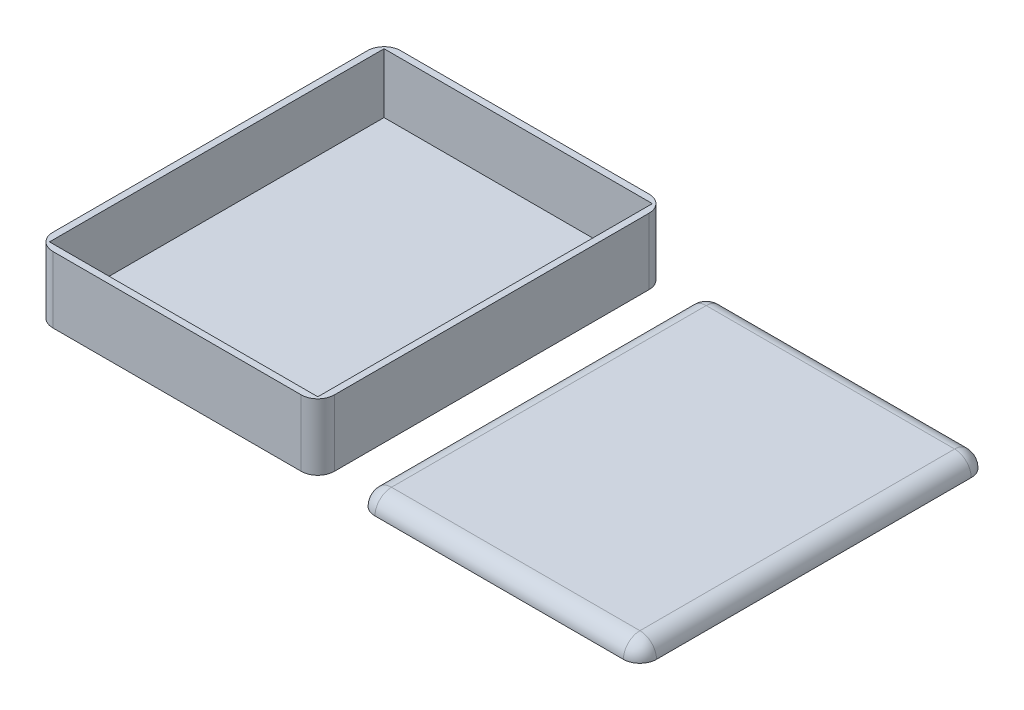
SolidWorks part; units mm, degrees
ref_plane "Front Plane" through (0, 0, 0) normal (0, 0, 1) x (1, 0, 0)
ref_plane "Top Plane" through (0, 0, 0) normal (0, 1, 0) x (1, 0, 0)
ref_plane "Right Plane" through (0, 0, 0) normal (1, 0, 0) x (0, 0, -1)
sketch "Sketch1" plane through (0, 0, 0) normal (0, 1, 0) x (1, 0, 0)
  line L1 (-42.5, -52.5) -> (42.5, -52.5)
  line L2 (-42.5, -52.5) -> (-42.5, 52.5)
  line L3 (-42.5, 52.5) -> (42.5, 52.5)
  line L4 (42.5, -52.5) -> (42.5, 52.5)
  line L5 (-42.5, -52.5) -> (42.5, 52.5) construction
  line L6 (-42.5, 52.5) -> (42.5, -52.5) construction
  point P0 (0, 0)
  dimension "D1" = 85
  dimension "D2" = 105
extrude "Boss-Extrude1" add sketch "Sketch1" along normal blind 20
shell "Shell1" thickness 2 removed face at (0, 20, 0)
sketch "Sketch2" plane through (11.5436, 0, 0) normal (0, 1, 0) x (1, 0, 0)
  line L1 (43.7365, 51.9703) -> (128.7365, 51.9703)
  line L2 (43.7365, 51.9703) -> (43.7365, -53.0297)
  line L3 (43.7365, -53.0297) -> (128.7365, -53.0297)
  line L4 (128.7365, 51.9703) -> (128.7365, -53.0297)
  dimension "D1" = 85
  dimension "D2" = 105
extrude "Boss-Extrude2" add sketch "Sketch2" along normal blind 5 separate body
fillet "Fillet1" radius 5 4 edges at (-42.5, 10, -52.5) (42.5, 10, -52.5) (42.5, 10, 52.5) (-42.5, 10, 52.5)
fillet "Fillet2" radius 5 4 edges at (55.2802, 2.5, -51.9703) (140.2802, 2.5, -51.9703) (140.2802, 2.5, 53.0297) (55.2802, 2.5, 53.0297)
fillet "Fillet3" radius 5 8 edges at (56.7446, 5, 51.5653) (55.2802, 5, 0.5297) (56.7446, 5, -50.5058) (97.7802, 5, -51.9703) (138.8157, 5, -50.5058) (140.2802, 5, 0.5297) (138.8157, 5, 51.5653) (97.7802, 5, 53.0297)
